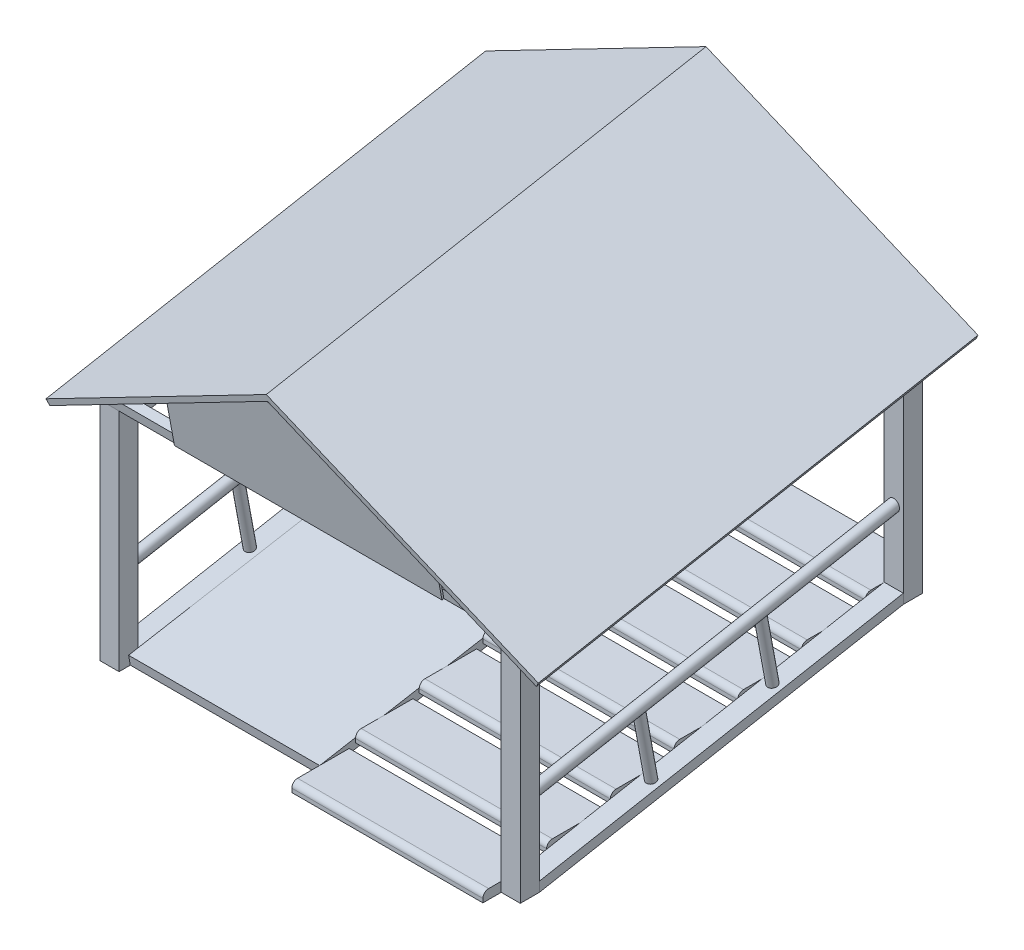
SolidWorks part; units mm, degrees
ref_plane "Front Plane" through (0, 0, 0) normal (0, 0, 1) x (1, 0, 0)
ref_plane "Top Plane" through (0, 0, 0) normal (0, 1, 0) x (1, 0, 0)
ref_plane "Right Plane" through (0, 0, 0) normal (1, 0, 0) x (0, 0, -1)
sketch "Sketch2" plane through (0, 0, 0) normal (1, 0, 0) x (0, 0, -1)
  line L0 (0, 0) -> (10000, 1763.2698)
  line L1 (55, 0) -> (-55, 0) construction
  line L2 (0, 0) -> (43.412, -246.2019)
  line L3 (43.412, -246.2019) -> (10043.412, 1517.0679)
  line L4 (10043.412, 1517.0679) -> (10000, 1763.2698)
  dimension "D1" = 10
  dimension "D2" = 10000
  dimension "D3" = 250
extrude "Boss-Extrude1" add sketch "Sketch2" along normal blind 5000 contours L0 L4 L3 L2
sketch "Sketch3" plane through (5000, 0, 0) normal (1, 0, 0) x (0, 0, -1)
  line L0 (21.706, -123.101) -> (10021.706, 1640.1688) construction
  line L1 (0, 0) -> (43.412, -246.2019) construction
  line L2 (10043.412, 1517.0679) -> (10000, 1763.2698) construction
sketch "Sketch4" plane through (5000, 0, 0) normal (1, 0, 0) x (0, 0, -1)
  line L0 (21.706, -123.101) -> (10021.706, 1640.1688) construction
  line L1 (771.706, -248.101) -> (-728.294, -248.101)
  line L2 (771.706, -248.101) -> (771.706, 1.899)
  line L3 (771.706, 1.899) -> (-728.294, 1.899)
  line L4 (-728.294, -248.101) -> (-728.294, 1.899)
  line L5 (771.706, -248.101) -> (-728.294, 1.899) construction
  line L6 (771.706, 1.899) -> (-728.294, -248.101) construction
  line L7 (9271.706, 1765.1688) -> (10771.706, 1765.1688)
  line L8 (938.3733, 295.7774) -> (2438.3733, 295.7774)
  line L9 (938.3733, 295.7774) -> (938.3733, 45.7774)
  line L10 (938.3733, 45.7774) -> (2438.3733, 45.7774)
  line L11 (2438.3733, 295.7774) -> (2438.3733, 45.7774)
  line L12 (938.3733, 295.7774) -> (2438.3733, 45.7774) construction
  line L13 (938.3733, 45.7774) -> (2438.3733, 295.7774) construction
  line L14 (2605.0406, 589.6559) -> (4105.0406, 589.6559)
  line L15 (2605.0406, 589.6559) -> (2605.0406, 339.6559)
  line L16 (2605.0406, 339.6559) -> (4105.0406, 339.6559)
  line L17 (4105.0406, 589.6559) -> (4105.0406, 339.6559)
  line L18 (2605.0406, 589.6559) -> (4105.0406, 339.6559) construction
  line L19 (2605.0406, 339.6559) -> (4105.0406, 589.6559) construction
  line L20 (4271.7079, 883.5343) -> (5771.7079, 883.5343)
  line L21 (4271.7079, 883.5343) -> (4271.7079, 633.5343)
  line L22 (4271.7079, 633.5343) -> (5771.7079, 633.5343)
  line L23 (5771.7079, 883.5343) -> (5771.7079, 633.5343)
  line L24 (4271.7079, 883.5343) -> (5771.7079, 633.5343) construction
  line L25 (4271.7079, 633.5343) -> (5771.7079, 883.5343) construction
  line L26 (9271.706, 1765.1688) -> (9271.706, 1515.1688)
  line L27 (5938.3752, 1177.4127) -> (7438.3752, 1177.4127)
  line L28 (5938.3752, 1177.4127) -> (5938.3752, 927.4127)
  line L29 (5938.3752, 927.4127) -> (7438.3752, 927.4127)
  line L30 (7438.3752, 1177.4127) -> (7438.3752, 927.4127)
  line L31 (5938.3752, 1177.4127) -> (7438.3752, 927.4127) construction
  line L32 (5938.3752, 927.4127) -> (7438.3752, 1177.4127) construction
  line L33 (7605.0425, 1471.2911) -> (9105.0425, 1471.2911)
  line L34 (7605.0425, 1471.2911) -> (7605.0425, 1221.2911)
  line L35 (7605.0425, 1221.2911) -> (9105.0425, 1221.2911)
  line L36 (9105.0425, 1471.2911) -> (9105.0425, 1221.2911)
  line L37 (7605.0425, 1471.2911) -> (9105.0425, 1221.2911) construction
  line L38 (7605.0425, 1221.2911) -> (9105.0425, 1471.2911) construction
  line L39 (9271.706, 1515.1688) -> (10771.706, 1515.1688)
  line L40 (10771.706, 1765.1688) -> (10771.706, 1515.1688)
  line L41 (9271.706, 1765.1688) -> (10771.706, 1515.1688) construction
  line L42 (9271.706, 1515.1688) -> (10771.706, 1765.1688) construction
  point P0 (21.706, -123.101)
  point P7 (1688.3733, 170.7774)
  point P13 (3355.0406, 464.6559)
  point P18 (5021.7079, 758.5343)
  point P23 (6688.3752, 1052.4127)
  point P28 (8355.0425, 1346.2911)
  point P33 (0, 0)
  point P34 (0, 0)
  point P35 (0, 0)
  point P36 (0, 0)
  point P37 (0, 0)
  point P42 (10021.706, 1640.1688)
  dimension "D1" = 250
  dimension "D2" = 1500
  dimension "D3" = 1500
  dimension "D4" = 1500
  dimension "D5" = 1500
  dimension "D6" = 1500
  dimension "D7" = 1500
  dimension "D8" = 250
  dimension "D9" = 250
  dimension "D10" = 250
  dimension "D11" = 250
  dimension "D12" = 250
  dimension "D13" = 1692.3783
  dimension "D14" = 1692.3783
  dimension "D15" = 1692.3783
  dimension "D16" = 1692.3783
  dimension "D17" = 1692.3783
  dimension "D18" = 1500
  dimension "D19" = 250
extrude "Boss-Extrude2" add sketch "Sketch4" along normal blind 5000 separate body contours L3 L4 L1 L2
fillet "Fillet1" radius 150 1 edges at (7500, 1.899, 728.294)
pattern_linear "LPattern6" count 7 spacing 1692.3783 along (0, 0.1736, -0.9848) of "Boss-Extrude2"
fillet "Fillet2" radius 150 1 edges at (7500, 295.7774, -938.3733)
fillet "Fillet3" radius 150 1 edges at (7500, 589.6559, -2605.0406)
fillet "Fillet4" radius 150 1 edges at (7500, 883.5343, -4271.7079)
fillet "Fillet5" radius 150 1 edges at (7500, 1177.4127, -5938.3752)
fillet "Fillet6" radius 150 1 edges at (7500, 1471.2911, -7605.0425)
fillet "Fillet7" radius 150 1 edges at (7500, 1765.1695, -9271.7098)
sketch "Sketch5" plane through (10000, 0, 0) normal (1, 0, 0) x (0, 0, -1)
  line L0 (771.706, -248.101) -> (-728.294, -248.101) construction
  line L1 (-250, -248.101) -> (250, -248.101)
  line L2 (-250, -248.101) -> (-250, 5659.3069)
  line L4 (250, -248.101) -> (250, 5751.899)
  line L5 (10771.7098, 1515.1695) -> (9271.7098, 1515.1695) construction
  line L6 (9771.7098, 1515.1695) -> (10271.7098, 1515.1695)
  line L7 (9771.7098, 1515.1695) -> (9771.7098, 7515.1695)
  line L9 (10271.7098, 1515.1695) -> (10271.7098, 7515.1695)
  line L10 (250, 5751.899) -> (9771.7098, 7515.1695)
  line L11 (9771.7098, 7515.1695) -> (10271.7098, 7607.7616)
  line L12 (10271.7098, 7607.7616) -> (10271.7098, 7515.1695)
  line L13 (250, 5751.899) -> (-250, 5659.3069)
  point P6 (0, -248.101)
  point P17 (10021.7098, 1515.1695)
  dimension "D1" = 6000
  dimension "D2" = 500
  dimension "D3" = 6000
  dimension "D4" = 500
  dimension "D5" = 500
extrude "Boss-Extrude3" add sketch "Sketch5" along normal blind 500 separate body contours L13 L2 L1 L4
extrude "Boss-Extrude4" add sketch "Sketch5<3>" along normal blind 500 separate body contours L11 L12 L9 L6 L7
sketch "Sketch5<3>" plane through (10000, 0, 0) normal (1, 0, 0) x (0, 0, -1) same geometry as "Sketch5"
sketch "Sketch6" plane through (10500, 0, 0) normal (1, 0, 0) x (0, 0, -1)
  line L0 (250, 5751.899) -> (9771.7098, 7515.1695) construction
  line L1 (250, 5751.899) -> (9771.7098, 7515.1695)
  line L2 (250, 5243.398) -> (9771.7098, 7006.6685)
  line L3 (250, -248.101) -> (250, 5751.899) construction
  line L4 (9771.7098, 1515.1695) -> (9771.7098, 7515.1695) construction
  line L5 (250, 5751.899) -> (250, 5243.398)
  line L6 (9771.7098, 7515.1695) -> (9771.7098, 7006.6685)
  dimension "D1" = 500
extrude "Boss-Extrude5" add sketch "Sketch6" against normal up to surface (500 mm away) contours L1 L6 L2 L5 up to face at (10000, 2728.751, 0)
mirror "Mirror1" about plane through (5000, 0, 0) normal (1, 0, 0) of bodies 117
ref_plane "Plane1" through (0, 142.8799, -771.5553) normal (0, 0.1821, -0.9833) x (-1, 0, 0)
sketch "Sketch7" plane through (0, 142.8799, -771.5553) normal (0, 0.1821, -0.9833) x (-1, 0, 0)
  line L0 (500, 5610.2177) -> (-10500, 5610.2177)
  line L1 (500, 5610.2177) -> (500, 5860.2177)
  line L2 (500, 5860.2177) -> (-5000, 9035.6442)
  line L3 (-5000, 9035.6442) -> (-10500, 5860.2177)
  line L4 (-10500, 5860.2177) -> (-10500, 5610.2177)
  point P8 (-5000, 5610.2177)
  point P13 (0, 0)
  dimension "D1" = 250
  dimension "D2" = 250
  dimension "D3" = 30
extrude "Boss-Extrude7" add sketch "Sketch7" along normal blind 250 separate body
sketch "Sketch8" plane through (0, 142.8799, -771.5553) normal (0, -0.1821, 0.9833) x (1, 0, 0)
  line L0 (5000, 8746.969) -> (0, 5860.2177)
  line L1 (0, 5860.2177) -> (10000, 5860.2177)
  line L2 (10000, 5860.2177) -> (5000, 8746.969)
  line L3 (5000, 9035.6442) -> (10500, 5860.2177) construction
  line L4 (-500, 5860.2177) -> (5000, 9035.6442) construction
  line L5 (10500, 5610.2177) -> (-500, 5610.2177) construction
  dimension "D1" = 250
  dimension "D2" = 250
  dimension "D3" = 250
extrude "Cut-Extrude1" cut sketch "Sketch8" against normal blind 250 contours L0 L1 L2
sketch "Sketch9" plane through (10500, 0, 0) normal (1, 0, 0) x (0, 0, -1)
  line L0 (5056.377, 6133.4632) -> (4965.3328, 6625.1043) construction
  line L1 (250, 5243.398) -> (9771.7098, 7006.6685) construction
  line L2 (10271.7098, 7607.7616) -> (-250, 5659.3069) construction
  line L3 (-250, 5405.0564) -> (10271.7098, 7353.5111) construction
  line L4 (-250, -248.101) -> (-250, 5659.3069) construction
  line L5 (10271.7098, 7607.7616) -> (10271.7098, 1515.1695) construction
  line L6 (10271.7098, 7607.7616) -> (-250, 5659.3069) construction
  point P14 (5010.8549, 6379.2838)
  point P15 (0, 0)
  point P16 (5010.8549, 6379.2838)
  point P17 (5056.377, 6133.4632)
  dimension "D1" = 250
ref_plane "Plane2" through (0, 1108.6773, -5986.8881) normal (0, 0.1821, -0.9833) x (0, 0.9833, 0.1821)
sketch "Sketch10" plane through (0, 142.8799, -771.5553) normal (0, -0.1821, 0.9833) x (1, 0, 0)
  line L0 (4875, 8674.8003) -> (4875, 5860.2177)
  line L1 (5000, 8746.969) -> (0, 5860.2177) construction
  line L2 (0, 5860.2177) -> (10000, 5860.2177) construction
  line L3 (5125, 8674.8003) -> (5125, 5860.2177)
  line L4 (10000, 5860.2177) -> (5000, 8746.969) construction
  line L5 (4875, 5860.2177) -> (5125, 5860.2177)
  line L6 (4875, 8674.8003) -> (5000, 8746.969)
  line L7 (5000, 8746.969) -> (5125, 8674.8003)
  point P10 (5000, 5860.2177)
  dimension "D1" = 250
extrude "Boss-Extrude8" add sketch "Sketch10" against normal up to surface (250 mm away) separate body up to face at (5000, 6896.8133, 224.9161)
sketch "Sketch11" plane through (0, 142.8799, -771.5553) normal (0, -0.1821, 0.9833) x (1, 0, 0)
  line L0 (1500, 7014.9182) -> (1500, 5610.2177)
  line L1 (-500, 5860.2177) -> (5000, 9035.6442) construction
  line L2 (10500, 5610.2177) -> (-500, 5610.2177) construction
  line L3 (1500, 5610.2177) -> (8500, 5610.2177)
  line L4 (8500, 5610.2177) -> (8500, 7014.9182)
  line L5 (5000, 9035.6442) -> (10500, 5860.2177) construction
  line L6 (-500, 5610.2177) -> (-500, 5860.2177) construction
  line L7 (10500, 5860.2177) -> (10500, 5610.2177) construction
  line L8 (6169.873, 8360.2177) -> (8500, 7014.9182)
  line L9 (1500, 7014.9182) -> (3830.127, 8360.2177)
  line L11 (3830.127, 8360.2177) -> (6169.873, 8360.2177)
  dimension "D1" = 2000
  dimension "D2" = 2000
  dimension "D3" = 2750
extrude "Boss-Extrude9" add sketch "Sketch11" along normal blind 50 separate body
combine bodies "Combine1" operation type add bodies to combine 125 123 121
ref_plane "Plane3" through (0, 2091.3346, -11293.2651) normal (0, 0.1821, -0.9833) x (-1, 0, 0)
sketch "Sketch12" plane through (0, 2091.3346, -11293.2651) normal (0, 0.1821, -0.9833) x (-1, 0, 0)
  line L5 (500, 5610.2177) -> (500, 5860.2177)
  line L6 (500, 5860.2177) -> (-5000, 9035.6442)
  line L7 (-5000, 9035.6442) -> (-10500, 5860.2177)
  line L8 (-10500, 5860.2177) -> (-10500, 5610.2177)
  line L9 (-10500, 5610.2177) -> (500, 5610.2177)
  line L10 (500, 5610.2177) -> (500, 5860.2177)
  line L11 (500, 5860.2177) -> (-5000, 9035.6442)
  line L12 (-5000, 9035.6442) -> (-10500, 5860.2177)
  line L13 (-10500, 5860.2177) -> (-10500, 5610.2177)
  line L14 (-10500, 5610.2177) -> (500, 5610.2177)
  dimension "D1" = 0
extrude "Boss-Extrude10" add sketch "Sketch12" against normal blind 250 separate body
sketch "Sketch13" plane through (0, 2091.3346, -11293.2651) normal (0, 0.1821, -0.9833) x (-1, 0, 0)
  line L0 (-4875, 8674.8003) -> (0, 5860.2177) construction
  line L1 (-4875, 8674.8003) -> (-4875, 5860.2177) construction
  line L2 (0, 5860.2177) -> (-4875, 5860.2177) construction
  line L3 (-5125, 5860.2177) -> (-10000, 5860.2177) construction
  line L4 (-10000, 5860.2177) -> (-5125, 8674.8003) construction
  line L5 (-5125, 5860.2177) -> (-5125, 8674.8003) construction
  line L6 (-4875, 8674.8003) -> (0, 5860.2177)
  line L7 (-4875, 8674.8003) -> (-4875, 5860.2177)
  line L8 (0, 5860.2177) -> (-4875, 5860.2177)
  line L9 (-5125, 5860.2177) -> (-10000, 5860.2177)
  line L10 (-10000, 5860.2177) -> (-5125, 8674.8003)
  line L11 (-5125, 5860.2177) -> (-5125, 8674.8003)
extrude "Cut-Extrude2" cut sketch "Sketch13" against normal blind 250
sketch "Sketch14" plane through (0, 2091.3346, -11293.2651) normal (0, 0.1821, -0.9833) x (-1, 0, 0)
  line L5 (-1500, 7014.9182) -> (-3830.127, 8360.2177)
  line L6 (-1500, 5610.2177) -> (-1500, 7014.9182)
  line L7 (-8500, 5610.2177) -> (-1500, 5610.2177)
  line L8 (-8500, 7014.9182) -> (-8500, 5610.2177)
  line L9 (-6169.873, 8360.2177) -> (-8500, 7014.9182)
  line L10 (-1500, 7014.9182) -> (-3830.127, 8360.2177)
  line L11 (-1500, 5610.2177) -> (-1500, 7014.9182)
  line L12 (-8500, 5610.2177) -> (-1500, 5610.2177)
  line L13 (-8500, 7014.9182) -> (-8500, 5610.2177)
  line L14 (-6169.873, 8360.2177) -> (-8500, 7014.9182)
  line L16 (-3830.127, 8360.2177) -> (-6169.873, 8360.2177)
  line L17 (-3830.127, 8360.2177) -> (-6169.873, 8360.2177)
  dimension "D1" = 0
extrude "Boss-Extrude11" add sketch "Sketch14" against normal blind 50 from surface separate body contours L17 L14 L13 L12 L11 L10 starting at face at (3250, 8730.5697, -9809.533)
sketch "Sketch15" plane through (0, 188.402, -1017.3758) normal (0, 0.1821, -0.9833) x (-1, 0, 0)
  line L0 (-5125, 8674.8003) -> (-5125, 8963.4754)
  line L1 (-5000, 9035.6442) -> (-10500, 5860.2177) construction
  line L2 (-4875, 8674.8003) -> (-4875, 8963.4754)
  line L3 (500, 5860.2177) -> (-5000, 9035.6442) construction
  line L4 (-5125, 8674.8003) -> (-4875, 8674.8003)
  line L5 (-4875, 8963.4754) -> (-5000, 9035.6442)
  line L6 (-5000, 9035.6442) -> (-5125, 8963.4754)
extrude "Boss-Extrude12" add sketch "Sketch15" along normal up to surface (10200.6006 mm away) separate body contours L0 L6 L5 L2 L4 up to face at (3250, 8730.5697, -9809.533)
sketch "Sketch16" plane through (0, 142.8799, -771.5553) normal (0, 0.1821, -0.9833) x (-1, 0, 0)
  line L0 (500, 5860.2177) -> (-5000, 9035.6442) construction
  line L1 (-5000, 9035.6442) -> (-10500, 5860.2177) construction
  line L2 (500, 5860.2177) -> (-5000, 9035.6442)
  line L3 (-5000, 9035.6442) -> (-10500, 5860.2177)
  line L4 (-10500, 5860.2177) -> (-11366.0254, 5360.2177)
  line L5 (-11366.0254, 5360.2177) -> (-11441.0254, 5490.1215)
  line L6 (-11441.0254, 5490.1215) -> (-5000, 9208.8493)
  line L7 (-5000, 9208.8493) -> (1441.0254, 5490.1215)
  line L8 (1441.0254, 5490.1215) -> (1366.0254, 5360.2177)
  line L9 (1366.0254, 5360.2177) -> (500, 5860.2177)
  point P2 (-5000, 9925.4519)
  point P9 (0, 0)
  dimension "D1" = 150
  dimension "D2" = 1000
  dimension "D3" = 1000
extrude "Boss-Extrude13" add sketch "Sketch16" along normal up to surface (10700.6006 mm away) separate body contours L6 L7 L8 L9 L2 L3 L4 L5 up to face at (3250, 8776.0918, -10055.3535)
extrude "Boss-Extrude14" add sketch "Sketch16<3>" against normal blind 500
sketch "Sketch16<3>" plane through (0, 142.8799, -771.5553) normal (0, 0.1821, -0.9833) x (-1, 0, 0) same geometry as "Sketch16"
extrude "Boss-Extrude15" add sketch "Sketch16<4>" along normal blind 500 from surface starting at face at (5000, 8637.5638, -10081.0067)
sketch "Sketch16<4>" plane through (0, 142.8799, -771.5553) normal (0, 0.1821, -0.9833) x (-1, 0, 0) same geometry as "Sketch16"
sketch "Sketch17" plane through (0, 142.8799, -771.5553) normal (0, 0.1821, -0.9833) x (-1, 0, 0)
  line L0 (-10500, -198.4312) -> (-10500, 5610.2177) construction
  line L1 (-10500, -198.4312) -> (-10000, -198.4312) construction
  circle A0 centre (-10250, 1801.5688) radius 150
  point P2 (0, 0)
  point P3 (0, 0)
  point P8 (-10250, -198.4312)
  dimension "D2" = 300
  dimension "D1" = 250
  dimension "D3" = 2000
extrude "Boss-Extrude16" add sketch "Sketch17" along normal up to surface and the other way up to surface separate body up to face at (10250, 4260.919, -9771.7098) other way up to face at (10250, 2497.6485, -250)
sketch "Sketch18" plane through (10500, 0, 0) normal (1, 0, 0) x (0, 0, -1)
  line L0 (250, -248.101) -> (9771.7098, 1515.1695)
  line L1 (250, 6.1495) -> (9771.7098, 1769.42)
  line L2 (250, -248.101) -> (250, 5243.398) construction
  line L3 (9771.7098, 1515.1695) -> (9771.7098, 7006.6685) construction
  line L4 (250, 6.1495) -> (250, -248.101)
  line L5 (9771.7098, 1769.42) -> (9771.7098, 1515.1695)
  dimension "D1" = 250
extrude "Boss-Extrude17" add sketch "Sketch18" along normal blind 500 from surface separate body contours L0 L5 L1 L4 starting at face at (10000, 465.8691, -3228.8274)
sketch "Sketch19" plane through (0, -38.8154, -7.188) normal (0, 0.9833, 0.1821) x (1, 0, 0)
  line L0 (10250, 246.9403) -> (10250, 9930.5389) construction
  line L1 (10500, 246.9403) -> (10000, 246.9403) construction
  line L2 (10500, 9930.5389) -> (10000, 9930.5389) construction
  circle A0 centre (10250, 3474.807) radius 125
  point P8 (0, 0)
  dimension "D1" = 250
  dimension "D2" = 3227.8667
extrude "Boss-Extrude18" add sketch "Sketch19" along normal up to surface (1691.0442 mm away) separate body up to face at (10250, 3489.2154, -9771.7098)
pattern_linear "LPattern7" count 2 spacing 3227.8667 along (0, 0.1821, -0.9833) of bodies 136
combine bodies "Combine2" operation type add bodies to combine 134 136 137
mirror "Mirror4" about plane through (5000, 0, 0) normal (1, 0, 0) of bodies 138 135
